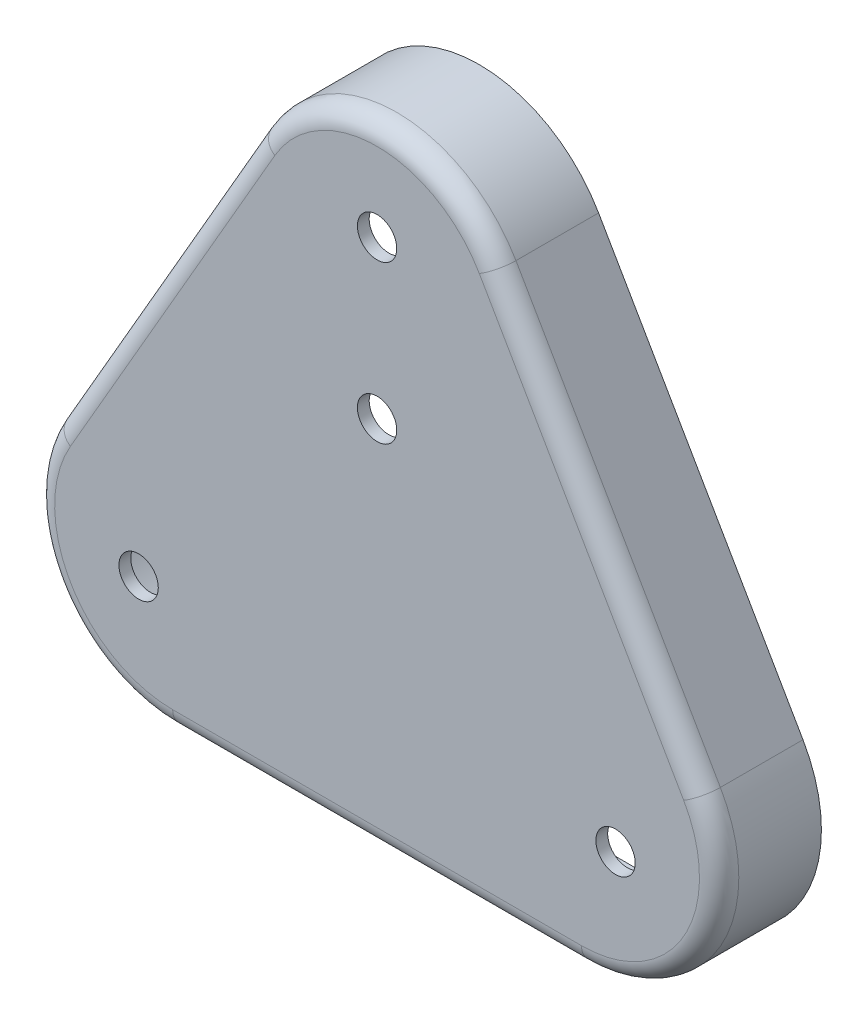
SolidWorks part; units mm, degrees
ref_plane "Plano frontal" through (0, 0, 0) normal (0, 0, 1) x (1, 0, 0)
ref_plane "Plano superior" through (0, 0, 0) normal (0, 1, 0) x (1, 0, 0)
ref_plane "Plano direito" through (0, 0, 0) normal (1, 0, 0) x (0, 0, -1)
sketch "Esboço1" plane through (0, 0, 0) normal (0, 0, 1) x (1, 0, 0)
  line L3 (51.9615, -65) -> (-51.9615, -65)
  line L4 (30.3109, 77.5) -> (82.2724, -12.5)
  line L5 (-82.2724, -12.5) -> (-30.3109, 77.5)
  line L9 (51.9615, -62) -> (-51.9615, -62)
  line L10 (-79.6743, -14) -> (-27.7128, 76)
  line L11 (27.7128, 76) -> (79.6743, -14)
  arc A3 (-82.2724, -12.5) -> (-51.9615, -65) centre (-51.9615, -30) ccw
  arc A4 (51.9615, -65) -> (82.2724, -12.5) centre (51.9615, -30) ccw
  arc A5 (30.3109, 77.5) -> (-30.3109, 77.5) centre (0, 60) ccw
  arc A9 (-79.6743, -14) -> (-51.9615, -62) centre (-51.9615, -30) ccw
  arc A10 (27.7128, 76) -> (-27.7128, 76) centre (0, 60) ccw
  arc A11 (51.9615, -62) -> (79.6743, -14) centre (51.9615, -30) ccw
  dimension "D1" = 3
extrude "Ressalto-extrusão1" add sketch "Esboço1" along normal blind 3
sketch "Esboço2" plane through (0, 0, 3) normal (0, 0, 1) x (1, 0, 0)
  line L0 (-51.9615, -65) -> (51.9615, -65) construction
  line L1 (82.2724, -12.5) -> (30.3109, 77.5) construction
  line L2 (-30.3109, 77.5) -> (-82.2724, -12.5) construction
  line L3 (-51.9615, -65) -> (51.9615, -65)
  line L4 (82.2724, -12.5) -> (30.3109, 77.5)
  line L5 (-30.3109, 77.5) -> (-82.2724, -12.5)
  line L6 (-51.9615, -61) -> (51.9615, -61)
  line L7 (78.8083, -14.5) -> (26.8468, 75.5)
  line L8 (-26.8468, 75.5) -> (-78.8083, -14.5)
  arc A0 (-82.2724, -12.5) -> (-51.9615, -65) centre (-51.9615, -30) ccw construction
  arc A1 (51.9615, -65) -> (82.2724, -12.5) centre (51.9615, -30) ccw construction
  arc A2 (30.3109, 77.5) -> (-30.3109, 77.5) centre (0, 60) ccw construction
  arc A3 (-82.2724, -12.5) -> (-51.9615, -65) centre (-51.9615, -30) ccw
  arc A4 (51.9615, -65) -> (82.2724, -12.5) centre (51.9615, -30) ccw
  arc A5 (30.3109, 77.5) -> (-30.3109, 77.5) centre (0, 60) ccw
  arc A6 (51.9615, -61) -> (78.8083, -14.5) centre (51.9615, -30) ccw
  arc A7 (26.8468, 75.5) -> (-26.8468, 75.5) centre (0, 60) ccw
  arc A8 (-78.8083, -14.5) -> (-51.9615, -61) centre (-51.9615, -30) ccw
  dimension "D1" = 4
extrude "Ressalto-extrusão2" add sketch "Esboço2" along normal blind 20
sketch "Esboço3" plane through (0, 0, 23) normal (0, 0, 1) x (1, 0, 0)
  line L0 (-30.3109, 77.5) -> (-82.2724, -12.5) construction
  line L1 (-51.9615, -65) -> (51.9615, -65) construction
  line L2 (82.2724, -12.5) -> (30.3109, 77.5) construction
  line L3 (-30.3109, 77.5) -> (-82.2724, -12.5)
  line L4 (-51.9615, -65) -> (51.9615, -65)
  line L5 (82.2724, -12.5) -> (30.3109, 77.5)
  arc A0 (-82.2724, -12.5) -> (-51.9615, -65) centre (-51.9615, -30) ccw construction
  arc A1 (51.9615, -65) -> (82.2724, -12.5) centre (51.9615, -30) ccw construction
  arc A2 (30.3109, 77.5) -> (-30.3109, 77.5) centre (0, 60) ccw construction
  arc A3 (-82.2724, -12.5) -> (-51.9615, -65) centre (-51.9615, -30) ccw
  arc A4 (51.9615, -65) -> (82.2724, -12.5) centre (51.9615, -30) ccw
  arc A5 (30.3109, 77.5) -> (-30.3109, 77.5) centre (0, 60) ccw
extrude "Ressalto-extrusão3" add sketch "Esboço3" along normal blind 3
sketch "Esboço4" plane through (0, 0, 26) normal (0, 0, 1) x (1, 0, 0)
  line L0 (0, 0) -> (0, 70) construction
  circle A3 centre (0, 70) radius 5
  circle A4 centre (60.6218, -35) radius 5
  circle A5 centre (-60.6218, -35) radius 5
  circle A6 centre (0, 30) radius 5
  point P13 (0, 0)
  dimension "D1" = 70
  dimension "D2" = 10
  dimension "D4" = 10
  dimension "D5" = 30
  dimension "D3" = 3
extrude "Corte-extrusão1" cut sketch "Esboço4" against normal up to surface (3 mm away) up to face at (0, 0, 23)
fillet "Filete1" radius 5 6 edges at (82.2724, -47.5, 26) (0, -65, 26) (-82.2724, -47.5, 26) (-56.2917, 32.5, 26) (0, 95, 26) (56.2917, 32.5, 26)
